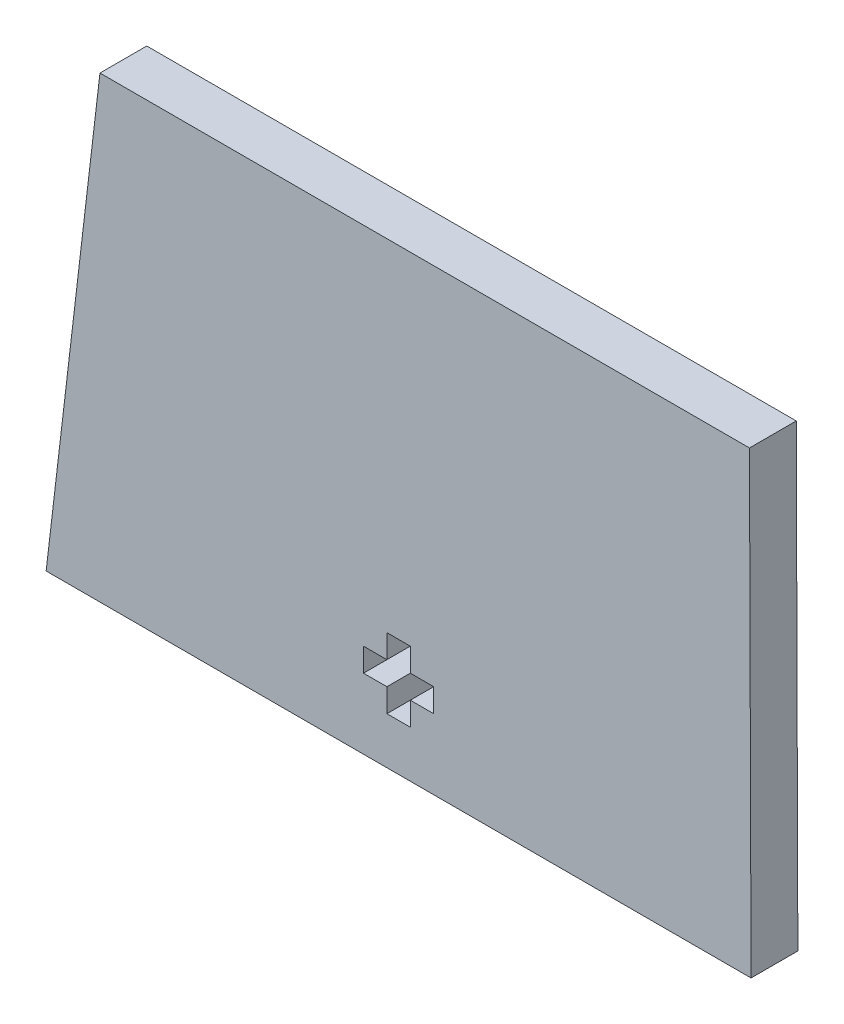
SolidWorks part; units mm, degrees
ref_plane "Ebene vorne" through (0, 0, 0) normal (0, 0, 1) x (1, 0, 0)
ref_plane "Ebene oben" through (0, 0, 0) normal (0, 1, 0) x (1, 0, 0)
ref_plane "Ebene rechts" through (0, 0, 0) normal (1, 0, 0) x (0, 0, -1)
sketch "Skizze1" plane through (0, 0, 0) normal (0, 0, 1) x (1, 0, 0)
  line L0 (0, 0) -> (2.3002, 19.5804)
  line L1 (2.3002, 19.5804) -> (30.0566, 19.5829)
  line L2 (30.0566, 19.5829) -> (30.125, 0)
  line L3 (30.125, 0) -> (0, 0)
  dimension "D1" = 30.125
  dimension "D2" = 19.583
  dimension "D3" = 19.715
  dimension "D4" = 83.3
  dimension "D5" = 89.8
extrude "Aufsatz-Linear austragen1" add sketch "Skizze1" along normal blind 2
sketch "Skizze4" plane through (0, 0, 0) normal (0, 0, 1) x (1, 0, 0)
  line L1 (0, 0) -> (30, 0)
  line L2 (0, 0) -> (0, 20)
  line L3 (0, 20) -> (30, 20)
  line L4 (30, 0) -> (30, 20)
  dimension "D1" = 30
  dimension "D2" = 20
sketch "Skizze2" plane through (0, 0, 2) normal (0, 0, 1) x (1, 0, 0)
  circle A0 centre (16.1795, 8.0246) radius 18.0602
sketch "Skizze3" plane through (0, 0, 2) normal (0, 0, 1) x (1, 0, 0)
  line L0 (2.1784, 0.7914) -> (30.1784, 0.7914)
  line L1 (2.1784, 0.7914) -> (2.1784, 18.7914)
  line L2 (30.1784, 0.7914) -> (30.1784, 18.7914)
  line L3 (2.1784, 18.7914) -> (30.1784, 18.7914)
  line L4 (2.1784, 0.7914) -> (30.1784, 18.7914) construction
  line L5 (30.1784, 0.7914) -> (2.1784, 18.7914) construction
  line L6 (30.125, 0) -> (30.0566, 19.5829) construction
  line L7 (30.0566, 19.5829) -> (2.3002, 19.5804) construction
  point P1 (16.1784, 9.7914)
  point P8 (30.0908, 9.7914)
  point P11 (16.1784, 19.5816)
  dimension "D1" = 18
  dimension "D2" = 28
ref_point "SWASI_Vision_Point_1"
ref_point "SWASI_Vision_Point_1_helper"
ref_point "SWASI_Vision_Point_2"
ref_point "SWASI_Vision_Point_2_helper"
ref_point "SWASI_Vision_Point_3"
ref_point "SWASI_Vision_Point_3_helper"
ref_point "SWASI_Vision_Point_4"
ref_plane "SWASI_Alignment_Plane_1" through (0, 0, 0) normal (0, -1, 0) x (-1, 0, 0)
ref_plane "SWASI_Alignment_Plane_2" through (0, 0, 2) normal (0, 0, -1) x (-1, 0, 0)
ref_axis "Achse3" through (0, 0, 2) along (0.9978, 0, -0.0662)
ref_axis "Achse4" through (0, 0, 0) along (0.9978, 0, 0.0662)
ref_point "SWASI_Surface_Center_Point"
ref_axis "SWASI_Norm_Alignment_Plane_3" through (30.125, 0, 0) along (-1, 0, 0)
ref_plane "SWASI_Alignment_Plane_3_G" through (15.0625, 0, 1) normal (-1, 0, 0) x (0, 0, 1)
sketch "Skizze5" plane through (0, 0, 2) normal (0, 0, 1) x (1, 0, 0)
  line L0 (14.5625, 3) -> (13.5625, 3)
  line L1 (13.5625, 3) -> (13.5625, 4)
  line L2 (13.5625, 4) -> (14.5625, 4)
  line L3 (14.5625, 4) -> (14.5625, 5)
  line L4 (14.5625, 5) -> (15.5625, 5)
  line L5 (15.5625, 5) -> (15.5625, 4)
  line L6 (15.5625, 4) -> (16.5625, 4)
  line L7 (16.5625, 4) -> (16.5625, 3)
  line L8 (16.5625, 3) -> (15.5625, 3)
  line L9 (15.5625, 3) -> (15.5625, 2)
  line L10 (15.5625, 2) -> (14.5625, 2)
  line L11 (14.5625, 2) -> (14.5625, 3)
  line L12 (0, 0) -> (30.125, 0) construction
  line L13 (15.0625, 0) -> (15.0625, 2)
  point P14 (16.5625, 8.2564)
  point P15 (16.5625, 3.5)
  dimension "D1" = 1
  dimension "D2" = 3.5
  dimension "D3" = 1
extrude "Schnitt-Linear austragen1" cut sketch "Skizze5" against normal through all contours L11 L10 L9 L8 L7 L6 L5 L4 L3 L2 L1 L0 region at (15.0625, 3.5, 2)
